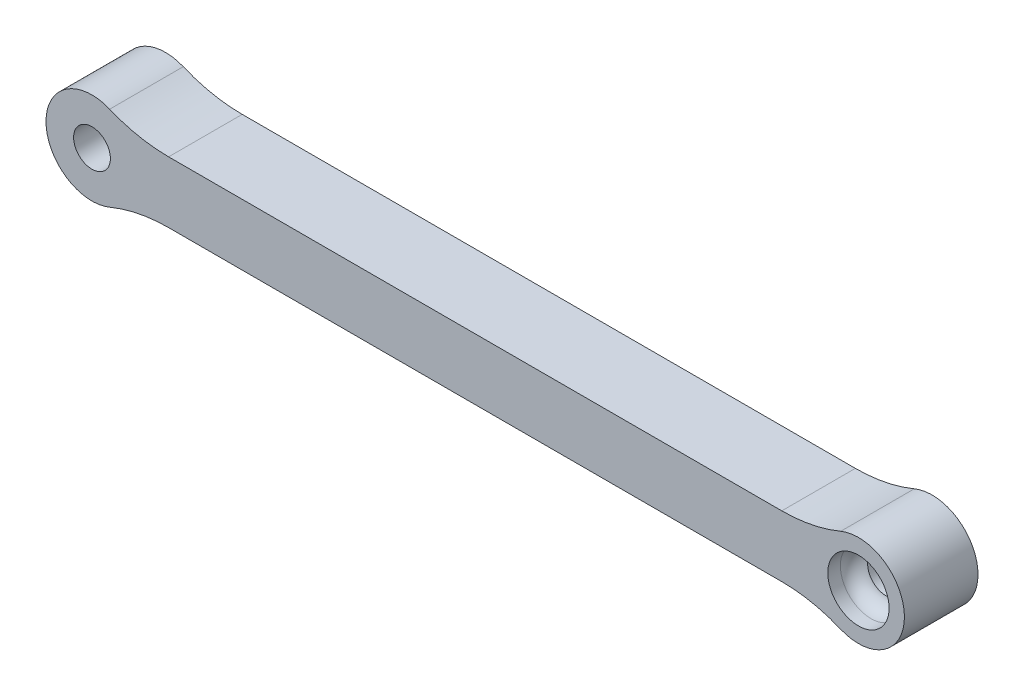
SolidWorks part; units mm, degrees
ref_plane "Front Plane" through (0, 0, 0) normal (0, 0, 1) x (1, 0, 0)
ref_plane "Top Plane" through (0, 0, 0) normal (0, 1, 0) x (1, 0, 0)
ref_plane "Right Plane" through (0, 0, 0) normal (1, 0, 0) x (0, 0, -1)
sketch "Sketch1" plane through (0, 0, 0) normal (0, 0, 1) x (1, 0, 0)
  line L0 (0, 0) -> (47, 0) construction
  line L1 (55, 0) -> (-55, 0) construction
  line L2 (5, -2) -> (45, -2)
  line L3 (5, 2) -> (45, 2)
  line L4 (0, 2) -> (50, 2) construction
  line L5 (0, -2) -> (50, -2) construction
  line L6 (48.8, 0) -> (50, 0) construction
  line L7 (0, 0) -> (50, 0) construction
  circle A0 centre (0, 0) radius 1.2
  circle A1 centre (50, 0) radius 1.2
  arc A2 (1.1538, 2.7692) -> (1.1538, -2.7692) centre (0, 0) ccw
  arc A4 (5, 2) -> (1.1538, 2.7692) centre (5, 12) cw
  arc A5 (5, -2) -> (1.1538, -2.7692) centre (5, -12) ccw
  arc A6 (45, 2) -> (48.8462, 2.7692) centre (45, 12) ccw
  arc A8 (48.8462, -2.7692) -> (48.8462, 2.7692) centre (50, 0) ccw
  arc A9 (48.8462, -2.7692) -> (45, -2) centre (45, -12) ccw
  dimension "D1" = 2
  dimension "D3" = 10
  dimension "D4" = 10
  dimension "D5" = 10
  dimension "D6" = 10
  dimension "D2" = 2
extrude "Boss-Extrude1" add sketch "Sketch1" along normal blind 4.8
sketch "Sketch2" plane through (0, 0, 4.8) normal (0, 0, 1) x (1, 0, 0)
  circle A0 centre (50, 0) radius 2
extrude "Cut-Extrude1" cut sketch "Sketch2" against normal blind 1.8
fillet "Fillet1" radius 1 1 edges at (52, 0, 3)
